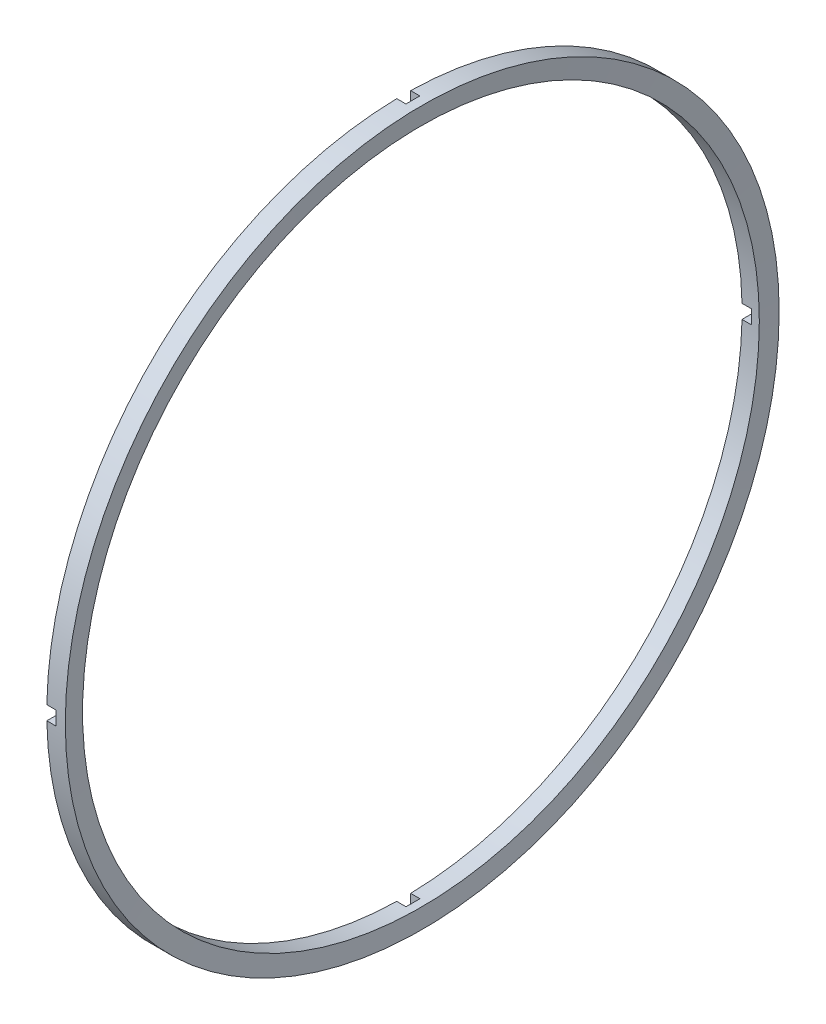
SolidWorks part; units mm, degrees
material "2018 slitina"
ref_plane "Přední rovina" through (0, 0, 0) normal (0, 0, 1) x (1, 0, 0)
ref_plane "Horní rovina" through (0, 0, 0) normal (0, 1, 0) x (1, 0, 0)
ref_plane "Pravá rovina" through (0, 0, 0) normal (1, 0, 0) x (0, 0, -1)
sketch "Skica1" plane through (0, 0, 0) normal (0, 0, 1) x (1, 0, 0)
  line L0 (-19.644, 38.5) -> (-19.644, 36.5)
  line L2 (-19.644, 36.5) -> (-17.7838, 36.5)
  line L3 (-17.7838, 36.5) -> (-17.644, 38.5)
  line L4 (-17.644, 38.5) -> (-19.644, 38.5)
  line L5 (-17.6789, 38) -> (-17.7838, 36.5) construction
  line L6 (0, 0) -> (-61.6382, 0) construction
  dimension "D1" = 77
  dimension "D2" = 2
  dimension "D3" = 2
revolve "Rotovat1" add sketch "Skica1" angle 360 about L6
cosmetic thread "Kosmetický závit1" parameters "D2"=76.18
sketch "Skica2" plane through (-19.644, 0, 0) normal (-1, 0, 0) x (0, 0, 1)
  line L1 (-0.75, -38.5) -> (0.75, -38.5)
  line L2 (-0.75, -38.5) -> (-0.75, 38.5)
  line L3 (-0.75, 38.5) -> (0.75, 38.5)
  line L4 (0.75, -38.5) -> (0.75, 38.5)
  line L5 (-0.75, -38.5) -> (0.75, 38.5) construction
  line L6 (-0.75, 38.5) -> (0.75, -38.5) construction
  line L7 (-38.5, -0.75) -> (38.5, -0.75)
  line L8 (-38.5, -0.75) -> (-38.5, 0.75)
  line L9 (-38.5, 0.75) -> (38.5, 0.75)
  line L10 (38.5, -0.75) -> (38.5, 0.75)
  line L11 (-38.5, -0.75) -> (38.5, 0.75) construction
  line L12 (-38.5, 0.75) -> (38.5, -0.75) construction
  circle A0 centre (0, 0) radius 38.5 construction
  point P0 (0, 0)
  point P8 (0, 0)
  circle M5 centre (0, 0) radius 36.5
  dimension "D1" = 1.5
extrude "Odebrat vysunutím1" cut sketch "Skica2" against normal blind 1 contours L2 L9 L4 M5 | L9 L4 L7 M5 | L2 L1 L4 L3 | L8 L7 L10 L9 region at (-19.644, 0, 18.6237) region at (-19.644, 18.6237, 0)
